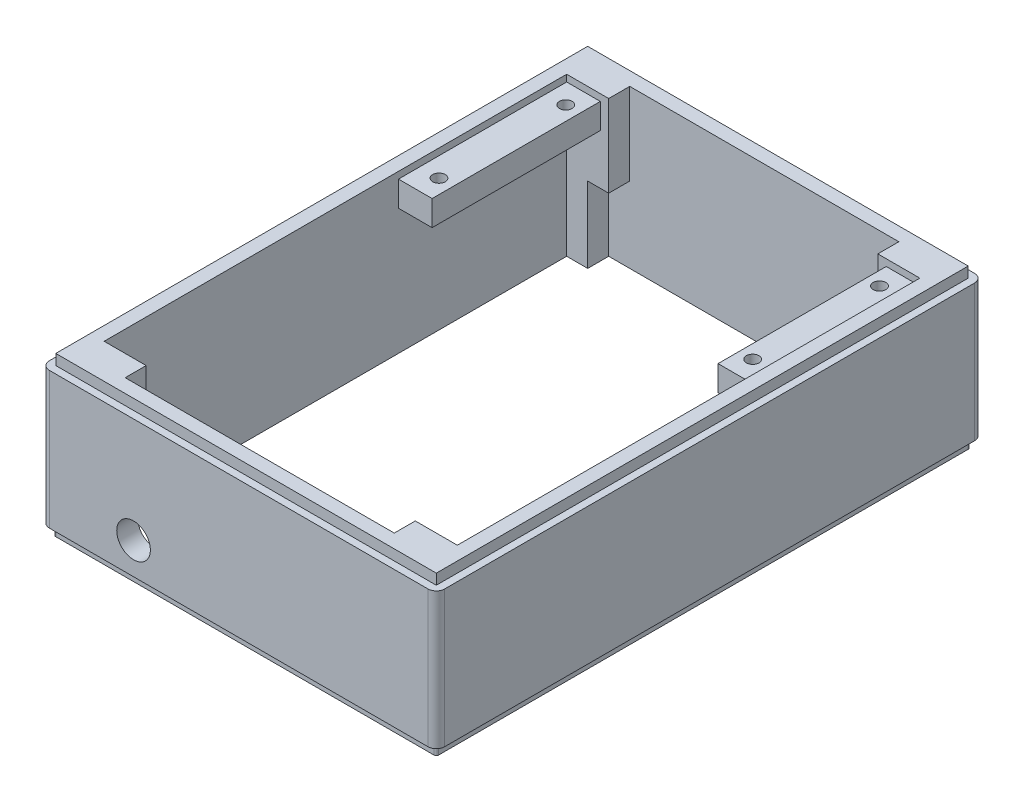
SolidWorks part; units mm, degrees
ref_plane "Front Plane" through (0, 0, 0) normal (0, 0, 1) x (1, 0, 0)
ref_plane "Top Plane" through (0, 0, 0) normal (0, 1, 0) x (1, 0, 0)
ref_plane "Right Plane" through (0, 0, 0) normal (1, 0, 0) x (0, 0, -1)
ref_plane "Plane1" through (0, 0, 0) normal (0, -1, 0) x (1, 0, 0)
sketch "Sketch1" plane through (0, 0, 0) normal (0, -1, 0) x (1, 0, 0)
  line L0 (94, 0) -> (0, 0)
  line L1 (0, 0) -> (0, -130)
  line L2 (0, -130) -> (94, -130)
  line L3 (94, -130) -> (94, 0)
extrude "Boss-Extrude1" add sketch "Sketch1" against normal blind 35
sketch "Sketch2" plane through (0, 35, 0) normal (0, 1, 0) x (-1, 0, 0)
  line L0 (-1.75, -128.25) -> (-92.25, -128.25)
  line L1 (-92.25, -128.25) -> (-92.25, -1.75)
  line L2 (-92.25, -1.75) -> (-1.75, -1.75)
  line L3 (-1.75, -1.75) -> (-1.75, -128.25)
extrude "Boss-Extrude2" add sketch "Sketch2" along normal blind 2.5
sketch "Sketch3" plane through (0, 37.5, 0) normal (0, 1, 0) x (-1, 0, 0)
  line L1 (-83, -120) -> (-79, -120)
  line L2 (-79, -120) -> (-79, -125)
  line L3 (-79, -125) -> (-15, -125)
  line L4 (-15, -125) -> (-15, -120)
  line L5 (-15, -120) -> (-5, -120)
  line L6 (-5, -120) -> (-5, -10)
  line L7 (-5, -10) -> (-15, -10)
  line L8 (-15, -10) -> (-15, -5)
  line L9 (-15, -5) -> (-79, -5)
  line L10 (-79, -5) -> (-79, -10)
  line L11 (-79, -10) -> (-89, -10)
  line L12 (-89, -10) -> (-89, -96)
  line L14 (-83, -120) -> (-89, -120)
  line L15 (-89, -120) -> (-89, -96)
extrude "Cut-Extrude1" cut sketch "Sketch3" against normal through all
sketch "Sketch4" plane through (0, 0, -10) normal (0, 0, -1) x (-1, 0, 0)
  line L0 (-15, 0) -> (-10, 0)
  line L1 (-10, 0) -> (-10, 18)
  line L2 (-10, 18) -> (-15, 18)
  line L3 (-15, 18) -> (-15, 0)
extrude "Cut-Extrude2" cut sketch "Sketch4" against normal blind 5
ref_plane "Plane2" through (0, 33.5, 0) normal (0, 1, 0) x (1, 0, 0)
ref_plane "Plane3" through (0, 31.5, 0) normal (0, -1, 0) x (1, 0, 0)
sketch "Sketch9" plane through (0, 0, -10) normal (0, 0, -1) x (-1, 0, 0)
  line L0 (-79, 18) -> (-84, 18)
  line L1 (-84, 18) -> (-84, 0)
  line L2 (-84, 0) -> (-79, 0)
  line L3 (-79, 0) -> (-79, 18)
extrude "Cut-Extrude6" cut sketch "Sketch9" against normal blind 5
sketch "Sketch11" plane through (0, 0, 0) normal (0, -1, 0) x (1, 0, 0)
  line L0 (15, -125) -> (15, -120)
  line L1 (15, -120) -> (10, -120)
  line L2 (10, -120) -> (10, -125)
  line L3 (10, -125) -> (15, -125)
extrude "Cut-Extrude8" cut sketch "Sketch11" against normal blind 18
sketch "Sketch12" plane through (0, 0, -120) normal (0, 0, 1) x (1, 0, 0)
  line L0 (79, 0) -> (84, 0)
  line L1 (84, 0) -> (84, 18)
  line L2 (84, 18) -> (79, 18)
  line L3 (79, 18) -> (79, 0)
extrude "Cut-Extrude9" cut sketch "Sketch12" against normal blind 5
hole_wizard "Ø8.0 (8) Diameter Hole1" positions "Sketch14" profile "Sketch13" hole size "Ø8.0" standard "ANSI Metric"
sketch "Sketch14" plane through (0, 0, -5) normal (0, 0, -1) x (-1, 0, 0)
  point P0 (-22, 10)
sketch "Sketch13" plane through (22, 10, -5) normal (1, 0, 0) x (0, 1, 0)
  line L0 (0, 0) -> (0, 5)
  line L1 (0, 5) -> (4, 5)
  line L2 (4, 5) -> (4, 0)
  line L5 (4, 0) -> (0, 0)
  line L11 (0, -6.35) -> (0, 107.95) construction
  dimension "Thru Hole Dia." = 8
  dimension "Thru Hole Depth" = 5
ref_plane "Plane4" through (0, 29.5, 0) normal (0, -1, 0) x (1, 0, 0)
fillet "Fillet1" radius 2 4 edges at (0, 17.5, -130) (94, 17.5, -130) (0, 17.5, 0) (94, 17.5, 0) tangent propagation no
sketch "Sketch16" plane through (0, 0, 0) normal (0, -1, 0) x (1, 0, 0)
  line L4 (1.5, -2) -> (1.5, -128)
  line L5 (2, -128.5) -> (92, -128.5)
  line L6 (92.5, -128) -> (92.5, -2)
  line L7 (92, -1.5) -> (2, -1.5)
  line L8 (0, -2) -> (0, -128)
  line L9 (2, -130) -> (92, -130)
  line L10 (94, -128) -> (94, -2)
  line L11 (92, 0) -> (2, 0)
  line L12 (0, -2) -> (0, -128)
  line L13 (2, -130) -> (92, -130)
  line L14 (94, -128) -> (94, -2)
  line L15 (92, 0) -> (2, 0)
  arc A4 (1.5, -128) -> (2, -128.5) centre (2, -128) ccw
  arc A5 (92, -128.5) -> (92.5, -128) centre (92, -128) ccw
  arc A6 (92.5, -2) -> (92, -1.5) centre (92, -2) ccw
  arc A7 (2, -1.5) -> (1.5, -2) centre (2, -2) ccw
  arc A8 (0, -128) -> (2, -130) centre (2, -128) ccw
  arc A9 (92, -130) -> (94, -128) centre (92, -128) ccw
  arc A10 (94, -2) -> (92, 0) centre (92, -2) ccw
  arc A11 (2, 0) -> (0, -2) centre (2, -2) ccw
  arc A12 (0, -128) -> (2, -130) centre (2, -128) ccw
  arc A13 (92, -130) -> (94, -128) centre (92, -128) ccw
  arc A14 (94, -2) -> (92, 0) centre (92, -2) ccw
  arc A15 (2, 0) -> (0, -2) centre (2, -2) ccw
  dimension "D1" = 0
  dimension "D2" = 1.5
extrude "Cut-Extrude10" cut sketch "Sketch16" against normal blind 2.5
sketch "Sketch17" plane through (5, 0, 0) normal (1, 0, 0) x (0, 0, -1)
  line L0 (120, 37.5) -> (10, 37.5) construction
  line L1 (120, 35.9) -> (80, 35.9)
  line L2 (120, 35.9) -> (120, 29.9)
  line L3 (120, 29.9) -> (80, 29.9)
  line L4 (80, 35.9) -> (80, 29.9)
  line L6 (120, 0) -> (120, 37.5) construction
  dimension "D1" = 40
  dimension "D2" = 6
  dimension "D3" = 1.6
extrude "Boss-Extrude3" add sketch "Sketch17" along normal blind 8
sketch "Sketch18" plane through (89, 0, 0) normal (-1, 0, 0) x (0, 0, 1)
  line L0 (-10, 37.5) -> (-120, 37.5) construction
  line L1 (-120, 29.9) -> (-80, 29.9)
  line L2 (-120, 29.9) -> (-120, 35.9)
  line L3 (-120, 35.9) -> (-80, 35.9)
  line L4 (-80, 29.9) -> (-80, 35.9)
  line L5 (-120, 0) -> (-120, 37.5) construction
  dimension "D1" = 6
  dimension "D2" = 40
  dimension "D3" = 1.6
extrude "Boss-Extrude4" add sketch "Sketch18" along normal blind 8
sketch "Sketch23" plane through (0, 35.9, 0) normal (0, 1, 0) x (1, 0, 0)
  circle A0 centre (9.6187, 115.175) radius 1.5
  circle A1 centre (9.6187, 85.0125) radius 1.5
  circle A2 centre (84.2312, 115.175) radius 1.5
  circle A3 centre (84.2312, 85.0125) radius 1.5
  dimension "D1" = 3
  dimension "D2" = 3
  dimension "D3" = 3
  dimension "D4" = 3
extrude "Cut-Extrude11" cut sketch "Sketch23" against normal blind 4.4
ref_plane "Plane5" through (0, 0, -5) normal (0, 0, -1) x (-1, 0, 0)
ref_axis "Axis1" through (22, 10, 0) along (0, 0, -1)
ref_point "Point1"
ref_plane "Plane6" through (0, 0, 0) normal (0, 0, 1) x (1, 0, 0)
ref_point "Point2"
